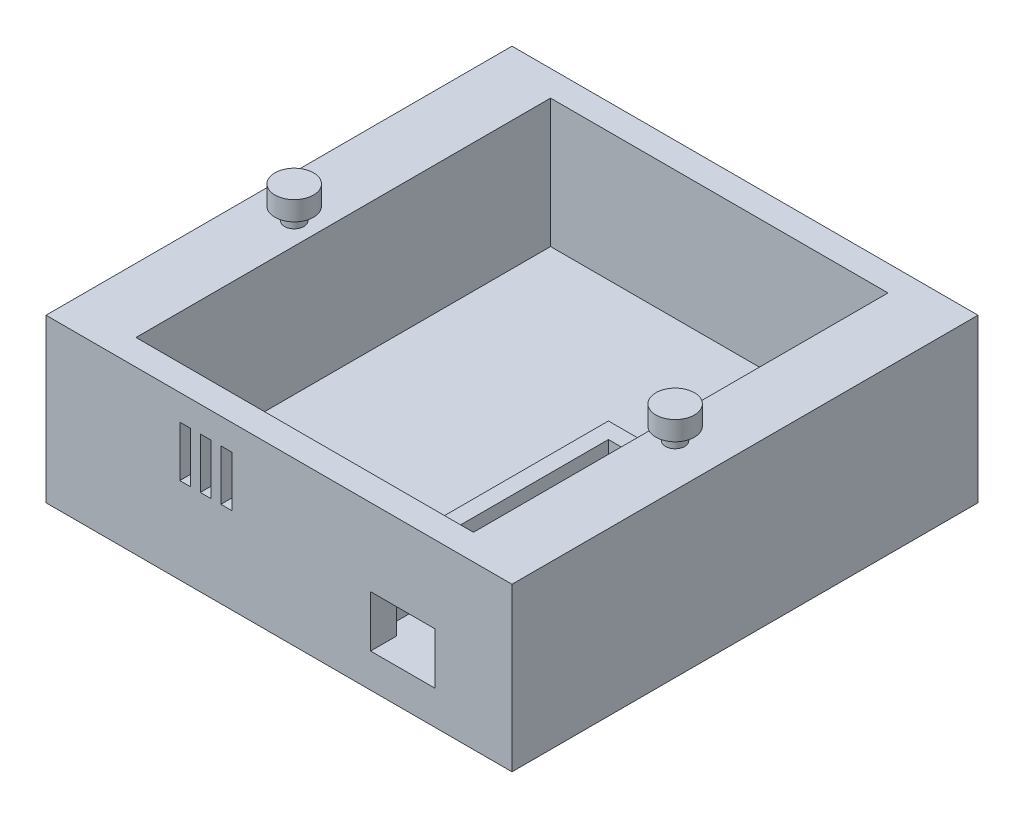
SolidWorks part; units mm, degrees
note: The reader was unsure of these and kept them because the rebuilt part matched: shared geometry of "Sketch4<3>".
ref_plane "Front Plane" through (0, 0, 0) normal (0, 0, 1) x (1, 0, 0)
ref_plane "Top Plane" through (0, 0, 0) normal (0, 1, 0) x (1, 0, 0)
ref_plane "Right Plane" through (0, 0, 0) normal (1, 0, 0) x (0, 0, -1)
sketch "Sketch1" plane through (0, 0, 0) normal (0, 1, 0) x (1, 0, 0)
  line L1 (0, 0) -> (92.075, 0)
  line L2 (0, 0) -> (0, 92.075)
  line L3 (0, 92.075) -> (92.075, 92.075)
  line L4 (92.075, 0) -> (92.075, 92.075)
  dimension "D1" = 92.075
  dimension "D2" = 92.075
extrude "Boss-Extrude1" add sketch "Sketch1" along normal blind 32.1 contours L3 L4 L1 L2
sketch "Sketch3" plane through (0, 32.1, 0) normal (0, 1, 0) x (1, 0, 0)
  line L0 (92.075, 0) -> (92.075, 92.075) construction
  line L1 (12.7, 5.08) -> (79.375, 5.08)
  line L2 (12.7, 5.08) -> (12.7, 86.995)
  line L3 (12.7, 86.995) -> (79.375, 86.995)
  line L4 (79.375, 5.08) -> (79.375, 86.995)
  line L5 (0, 0) -> (0, 92.075) construction
  line L6 (0, 0) -> (92.075, 0) construction
  line L7 (0, 92.075) -> (92.075, 92.075) construction
  dimension "D1" = 12.7
  dimension "D2" = 12.7
  dimension "D3" = 5.08
  dimension "D4" = 5.08
extrude "Cut-Extrude2" cut sketch "Sketch3" against normal blind 25.4
sketch "Sketch4" plane through (0, 32.1, 0) normal (0, 1, 0) x (1, 0, 0)
  line L0 (0, 92.075) -> (92.075, 92.075) construction
  line L7 (0, 0) -> (0, 92.075) construction
  line L12 (92.075, 0) -> (92.075, 92.075) construction
  circle A0 centre (8.405, 40.64) radius 1.905
  circle A1 centre (83.67, 40.64) radius 1.905
  dimension "D1" = 53.34
  dimension "D2" = 53.34
  dimension "D3" = 3.81
  dimension "D4" = 3.81
  dimension "D5" = 6.5
  dimension "D6" = 6.5
extrude "Boss-Extrude2" add sketch "Sketch4" along normal blind 2.54 contours A0
extrude "Boss-Extrude3" add sketch "Sketch4<3>" along normal blind 2.54
sketch "Sketch4<3>" plane through (0, 32.1, 0) normal (0, 1, 0) x (1, 0, 0) same geometry as "Sketch4"
sketch "Sketch8" plane through (0, 0, 0) normal (0, 0, 1) x (1, 0, 0)
  line L0 (0, 32.1) -> (92.075, 32.1) construction
  line L1 (26.4321, 27.02) -> (28.575, 27.02)
  line L2 (26.4321, 27.02) -> (26.4321, 17.02)
  line L3 (26.4321, 17.02) -> (28.575, 17.02)
  line L4 (28.575, 27.02) -> (28.575, 17.02)
  line L5 (92.075, 32.1) -> (92.075, 0) construction
  line L6 (30.4961, 27.02) -> (30.4961, 17.02)
  line L7 (30.4961, 27.02) -> (32.639, 27.02)
  line L8 (32.639, 27.02) -> (32.639, 17.02)
  line L9 (30.4961, 17.02) -> (32.639, 17.02)
  line L10 (34.5601, 27.02) -> (34.5601, 17.02)
  line L11 (34.5601, 27.02) -> (36.703, 27.02)
  line L12 (36.703, 27.02) -> (36.703, 17.02)
  line L13 (34.5601, 17.02) -> (36.703, 17.02)
  line L18 (26.4321, 27.02) -> (30.4961, 27.02) construction
  line L19 (40.767, 27.02) -> (40.767, 17.02) [skipped]
  line L20 (38.6241, 27.02) -> (40.767, 27.02) [skipped]
  line L21 (38.6241, 27.02) -> (38.6241, 17.02) [skipped]
  line L22 (38.6241, 17.02) -> (40.767, 17.02) [skipped]
  dimension "D4" = 63.5
  dimension "D1" = 2.1429
  dimension "D2" = 10
  dimension "D3" = 5.08
  dimension "D6" = 4.064
  dimension "D5" = 4
extrude "Cut-Extrude4" cut sketch "Sketch8" against normal blind 7
sketch "Sketch10" plane through (0, 6.7, 0) normal (0, 1, 0) x (1, 0, 0)
  line L0 (79.375, 5.08) -> (79.375, 86.995) construction
  line L2 (79.375, 49.53) -> (79.375, 52.705)
  line L5 (12.7, 5.08) -> (79.375, 5.08) construction
  line L6 (79.375, 5.08) -> (79.375, 86.995) construction
  line L12 (61.595, 52.705) -> (58.42, 52.705)
  line L13 (79.375, 49.53) -> (61.595, 49.53)
  line L14 (79.375, 49.53) -> (79.375, 52.705)
  line L15 (79.375, 52.705) -> (61.595, 52.705)
  line L16 (61.595, 49.53) -> (61.595, 52.705)
  line L17 (61.595, 52.705) -> (61.595, 5.08)
  line L18 (61.595, 5.08) -> (58.42, 5.08)
  line L19 (58.42, 52.705) -> (58.42, 5.08)
  dimension "D1" = 44.45
  dimension "D2" = 3.175
  dimension "D3" = 17.78
  dimension "D4" = 3.175
extrude "Boss-Extrude5" add sketch "Sketch10" along normal blind 10.16
sketch "Sketch11" plane through (0, 0, 0) normal (0, 0, 1) x (1, 0, 0)
  line L1 (64.135, 6.7) -> (76.835, 6.7)
  line L2 (64.135, 6.7) -> (64.135, 16.86)
  line L3 (64.135, 16.86) -> (76.835, 16.86)
  line L4 (76.835, 6.7) -> (76.835, 16.86)
  line L5 (61.595, 6.7) -> (79.375, 6.7) construction
  line L8 (61.595, 16.86) -> (61.595, 6.7) construction
  point P4 (63.3726, 6.7)
  dimension "D1" = 12.7
  dimension "D2" = 10.16
  dimension "D3" = 2.54
extrude "Cut-Extrude5" cut sketch "Sketch11" against normal blind 7.62
sketch "Sketch15" plane through (0, 34.64, 0) normal (0, 1, 0) x (1, 0, 0)
  circle A0 centre (8.405, 40.64) radius 3.81
  circle A1 centre (83.67, 40.64) radius 3.81
  dimension "D1" = 7.62
extrude "Boss-Extrude7" add sketch "Sketch15" along normal blind 3.81
